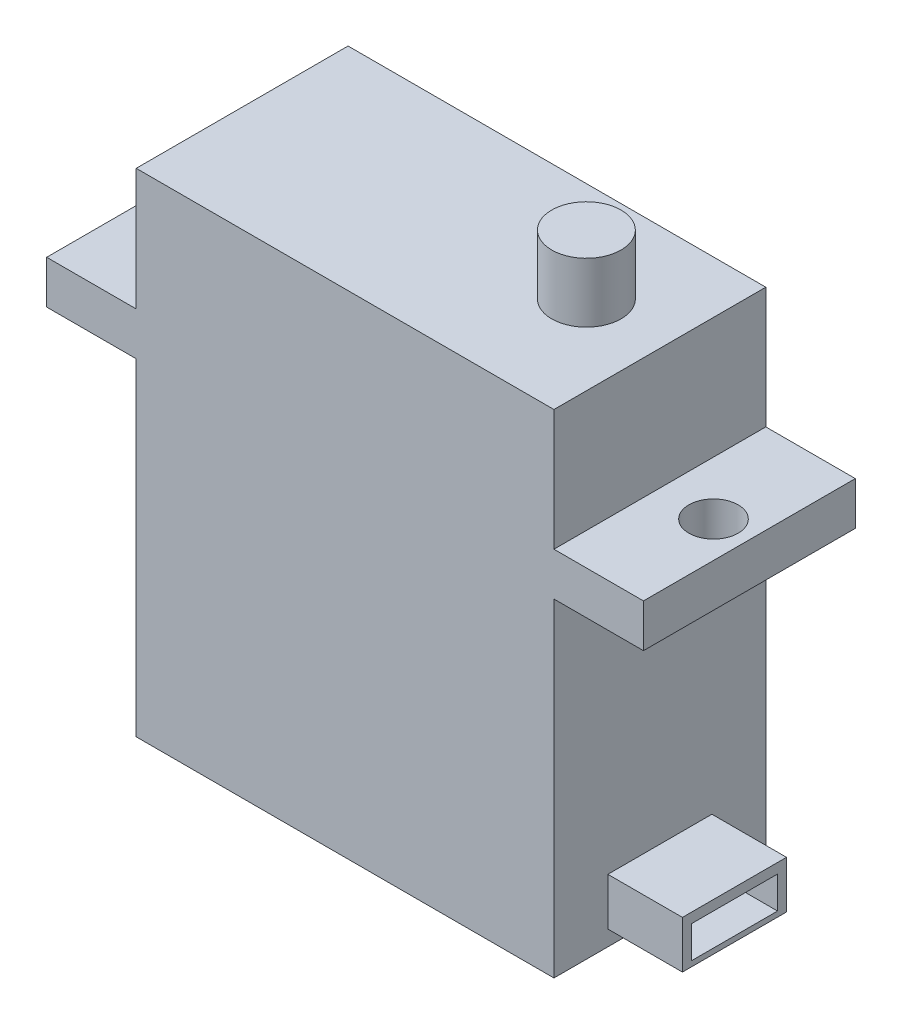
SolidWorks part; units mm, degrees
ref_plane "Front Plane" through (0, 0, 0) normal (0, 0, 1) x (1, 0, 0)
ref_plane "Top Plane" through (0, 0, 0) normal (0, 1, 0) x (1, 0, 0)
ref_plane "Right Plane" through (0, 0, 0) normal (1, 0, 0) x (0, 0, -1)
sketch "Sketch1" plane through (0, 0, 0) normal (0, 1, 0) x (1, 0, 0)
  line L1 (0, 0) -> (-28, 0)
  line L2 (0, 0) -> (0, 14.2)
  line L3 (0, 14.2) -> (-28, 14.2)
  line L4 (-28, 0) -> (-28, 14.2)
  dimension "D1" = 28
  dimension "D2" = 14.2
extrude "Boss-Extrude1" add sketch "Sketch1" along normal blind 33
sketch "Sketch2" plane through (0, 33, 0) normal (0, 1, 0) x (1, 0, 0)
  circle A0 centre (-5.3315, 7.5063) radius 2.3219
  dimension "D1" = 4.6438
extrude "Boss-Extrude3" add sketch "Sketch2" along normal blind 4
sketch "Sketch3" plane through (0, 0, 0) normal (1, 0, 0) x (0, 0, -1)
  line L1 (10.5874, 1.0363) -> (3.6126, 1.0363)
  line L2 (10.5874, 1.0363) -> (10.5874, 4.2126)
  line L3 (10.5874, 4.2126) -> (3.6126, 4.2126)
  line L4 (3.6126, 1.0363) -> (3.6126, 4.2126)
  line L5 (10.5874, 1.0363) -> (3.6126, 4.2126) construction
  line L6 (10.5874, 4.2126) -> (3.6126, 1.0363) construction
  point P0 (7.1, 2.6245)
  dimension "D1" = 24.485
  dimension "D2" = 6.9748
  dimension "D3" = 3.1763
  dimension "D4" = 6.9748
extrude "Boss-Extrude4" add sketch "Sketch3" along normal blind 5
sketch "Sketch4" plane through (5, 0, 0) normal (1, 0, 0) x (0, 0, -1)
  line L5 (4.2112, 1.393) -> (9.9888, 1.393)
  line L6 (4.2112, 1.393) -> (4.2112, 3.5428)
  line L7 (4.2112, 3.5428) -> (9.9888, 3.5428)
  line L8 (9.9888, 1.393) -> (9.9888, 3.5428)
  line L9 (4.2112, 1.393) -> (9.9888, 3.5428) construction
  line L10 (4.2112, 3.5428) -> (9.9888, 1.393) construction
  point P0 (7.1, 2.4679)
extrude "Cut-Extrude1" cut sketch "Sketch4" against normal blind 5
ref_plane "Plane1" through (-28, 0, 0) normal (0, 1, 0) x (1, 0, 0)
sketch "Sketch6" plane through (-28, 0, 0) normal (-1, 0, 0) x (0, 0, 1)
  line L0 (0, 0) -> (0, 21.9439)
  line L1 (0, 33) -> (0, 0) construction
  line L2 (0, 21.9439) -> (-14.2, 21.9439)
  line L3 (-14.2, 33) -> (-14.2, 0) construction
  line L5 (-14.2, 21.9439) -> (0, 21.9439)
  line L6 (-14.2, 21.9439) -> (-14.2, 24.8367)
  line L7 (-14.2, 24.8367) -> (0, 24.8367)
  line L8 (0, 21.9439) -> (0, 24.8367)
  line M3 (0, 0) -> (0, 33)
  line M5 (-14.2, 33) -> (-14.2, 0)
  dimension "D1" = 14.2
extrude "Boss-Extrude5" add sketch "Sketch6" along normal blind 6 contours L7 L2 M5 M3 region at (-28, 23.3903, -7.1)
sketch "Sketch11" plane through (0, 0, 0) normal (1, 0, 0) x (0, 0, -1)
  line L1 (0, 33) -> (0, 0) construction
  line L2 (14.2, 33) -> (14.2, 0) construction
  line L3 (0, 22) -> (14.2, 22)
  line L4 (0, 22) -> (0, 24.89)
  line L5 (0, 24.89) -> (14.2, 24.89)
  line L6 (14.2, 22) -> (14.2, 24.89)
extrude "Boss-Extrude6" add sketch "Sketch11" along normal blind 6 contours L4 L3 L6 L5
sketch "Sketch12" plane through (0, 24.89, 0) normal (0, 1, 0) x (1, 0, 0)
  circle A0 centre (3.5945, 7.1) radius 1.651
  dimension "D1" = 3.302
extrude "Cut-Extrude4" cut sketch "Sketch12" against normal blind 6
sketch "Sketch17" plane through (0, 24.8367, 0) normal (0, 1, 0) x (1, 0, 0)
  circle A0 centre (-31.3352, 7.1) radius 1.651
  dimension "D1" = 3.302
extrude "Cut-Extrude5" cut sketch "Sketch17" against normal through all
